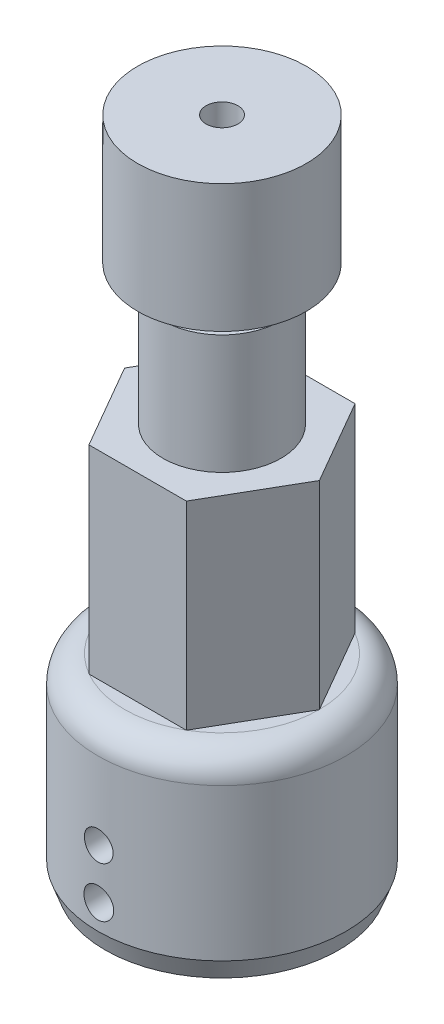
SolidWorks part; units mm, degrees
ref_plane "Front Plane" through (0, 0, 0) normal (0, 0, 1) x (1, 0, 0)
ref_plane "Top Plane" through (0, 0, 0) normal (0, 1, 0) x (1, 0, 0)
ref_plane "Right Plane" through (0, 0, 0) normal (1, 0, 0) x (0, 0, -1)
sketch "Sketch1" plane through (0, 0, 0) normal (0, 1, 0) x (1, 0, 0)
  line L0 (-1.8, 2.4) -> (1.8, 2.4)
  line L1 (9.815, 0) -> (4.9075, 8.5)
  line L2 (4.9075, 8.5) -> (-4.9075, 8.5)
  line L3 (-4.9075, 8.5) -> (-9.815, 0)
  line L4 (-9.815, 0) -> (-4.9075, -8.5)
  line L5 (-4.9075, -8.5) -> (4.9075, -8.5)
  line L6 (4.9075, -8.5) -> (9.815, 0)
  circle A0 centre (0, 0) radius 8.5 construction
  circle A1 centre (0, 0) radius 5.95
  circle A2 centre (0, 0) radius 3
  point P13 (0, 2.4)
  dimension "D2" = 11.9
  dimension "D3" = 6
  dimension "D1" = 17
  dimension "D4" = 2.4
extrude "Boss-Extrude1" add sketch "Sketch1" along normal blind 40 contours L5 L6 L1 L2 L3 L4 A1 region at (7.1363, 0, 4.1202)
extrude "Boss-Extrude2" add sketch "Sketch1<2>" along normal blind 52 contours A1 A2 | L0 A2 region at (0, 0, -2.6422) region at (-5.7817, 0, 0)
sketch "Sketch1<2>" plane through (0, 0, 0) normal (0, 1, 0) x (1, 0, 0) same geometry as "Sketch1"
sketch "Sketch2" plane through (0, 0, 0) normal (0, -1, 0) x (1, 0, 0)
  circle A0 centre (0, 0) radius 12.5
  line M1 (4.9075, 8.5) -> (-4.9075, 8.5)
  line M2 (-4.9075, 8.5) -> (-9.815, 0)
  line M3 (-9.815, 0) -> (-4.9075, -8.5)
  line M4 (-4.9075, -8.5) -> (4.9075, -8.5)
  line M5 (4.9075, -8.5) -> (9.815, 0)
  line M6 (9.815, 0) -> (4.9075, 8.5)
  dimension "D1" = 25
extrude "Boss-Extrude3" add sketch "Sketch2" against normal blind 15 contours A0 M1 M6 M5 M4 M3 M2 region at (-12.1464, 0, 0)
sketch "Sketch3" plane through (0, 0, 0) normal (0, 0, 1) x (1, 0, 0)
  line L0 (0, 40) -> (0, 0) construction
  line L1 (4.9075, 40) -> (-4.9075, 40) construction
  line L2 (12.5, 15) -> (-12.5, 15) construction
  line L3 (12.5, 2.2) -> (-12.5, 2.2) construction
  circle A0 centre (0, 9.5) radius 1.45
  circle A1 centre (0, 4.5) radius 1.5
  dimension "D2" = 2.9
  dimension "D3" = 3
  dimension "D4" = 5
  dimension "D5" = 5.5
  dimension "D1" = 12.8
extrude "Cut-Extrude1" cut sketch "Sketch3" against normal through all both and the other way through all
sketch "Sketch5" plane through (0, 15, 0) normal (0, 1, 0) x (1, 0, 0)
  circle A1 centre (0, 0) radius 12.5
  circle A2 centre (0, 0) radius 12.5
  line M2 (4.9075, -8.5) -> (-4.9075, -8.5)
  line M3 (-4.9075, -8.5) -> (-9.815, 0)
  line M4 (-9.815, 0) -> (-4.9075, 8.5)
  line M5 (-4.9075, 8.5) -> (4.9075, 8.5)
  line M6 (4.9075, 8.5) -> (9.815, 0)
  line M7 (9.815, 0) -> (4.9075, -8.5)
  circle M8 centre (0, 0) radius 12.5
  dimension "D1" = 0
extrude "Boss-Extrude4" add sketch "Sketch5" along normal blind 5 contours M8 M7 M2 M3 M4 M5 M6 region at (-12.1464, 15, 0)
sketch "Sketch6" plane through (0, 52, 0) normal (0, 1, 0) x (1, 0, 0)
  circle A0 centre (0, 0) radius 3
  circle A1 centre (0, 0) radius 1.5
  dimension "D1" = 3
sketch "Sketch7" plane through (0, 52, 0) normal (0, 1, 0) x (1, 0, 0)
  circle A0 centre (0, 0) radius 6
  circle A1 centre (0, 0) radius 8.5
  circle A3 centre (0, 0) radius 1.6
  dimension "D1" = 17
  dimension "D2" = 12
  dimension "D3" = 3.2
extrude "Boss-Extrude5" add sketch "Sketch7" along normal blind 15 separate body contours A1 A0 region at (-8.2596, 52, 0)
sketch "Sketch8" plane through (0, 67, 0) normal (0, 1, 0) x (1, 0, 0)
  circle A0 centre (0, 0) radius 6
  circle A1 centre (0, 0) radius 1.6
  dimension "D1" = 12
  dimension "D2" = 3.2
extrude "Boss-Extrude6" add sketch "Sketch8" against normal blind 3
sketch "Sketch9" plane through (0, 52, 0) normal (0, -1, 0) x (1, 0, 0)
  circle A1 centre (0, 0) radius 8.5
  circle A2 centre (0, 0) radius 8.5
  dimension "D1" = 0
extrude "Cut-Extrude4" cut sketch "Sketch9" against normal blind 2.1
extrude "Boss-Extrude7" add sketch "Sketch6" against normal blind 20
chamfer "Chamfer1" distance 4 angle 30 1 edges at (0, 32, 1.5) first distance on face at (0, 32, 1.5)
fillet "Fillet1" radius 2.7 1 edges at (0, 20, 12.5)
chamfer "Chamfer2" distance 2 angle 20 1 edges at (0, 0, -12.5) first distance on face at (0, 17.3, 12.5)
sketch "Sketch10" plane through (0, 0, 0) normal (0, -1, 0) x (1, 0, 0)
  line L0 (0, -11.7721) -> (0, 11.7721) construction
  line L1 (-11.7721, 0) -> (11.7721, 0) construction
  line L2 (-2.8, -8.25) -> (2.8, -8.25)
  line L3 (-2.8, -8.25) -> (-2.8, -5.75)
  line L4 (-2.8, -5.75) -> (2.8, -5.75)
  line L5 (2.8, -8.25) -> (2.8, -5.75)
  line L6 (-2.8, -8.25) -> (2.8, -5.75) construction
  line L7 (-2.8, -5.75) -> (2.8, -8.25) construction
  line L8 (-2.8, 5.75) -> (2.8, 5.75)
  line L9 (2.8, 8.25) -> (2.8, 5.75)
  line L10 (-2.8, 8.25) -> (2.8, 8.25)
  line L11 (-2.8, 8.25) -> (-2.8, 5.75)
  circle A0 centre (0, 0) radius 11.7721 construction
  point P5 (0, -7)
  dimension "D1" = 2.5
  dimension "D2" = 5.6
  dimension "D3" = 7
extrude "Cut-Extrude5" cut sketch "Sketch10" against normal blind 14
chamfer "Chamfer3" distance 2.5 angle 60 4 edges at (-2.8, 14, -7) (2.8, 14, -7) (2.8, 14, 7) (-2.8, 14, 7) first distance on face at (-2.8, 7, -7) first distance on face at (2.8, 7, -7) first distance on face at (2.8, 7, 7) first distance on face at (-2.8, 7, 7)
